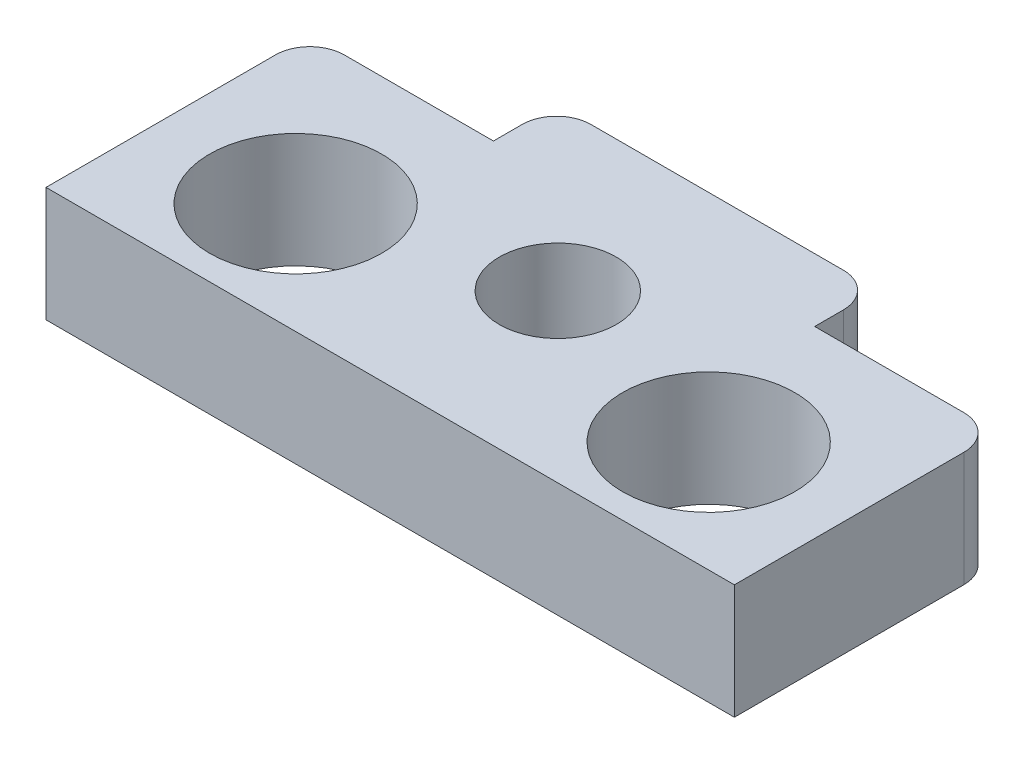
SolidWorks part; units mm, degrees
ref_plane "前视基准面" through (0, 0, 0) normal (0, 0, 1) x (1, 0, 0)
ref_plane "上视基准面" through (0, 0, 0) normal (0, 1, 0) x (1, 0, 0)
ref_plane "右视基准面" through (0, 0, 0) normal (1, 0, 0) x (0, 0, -1)
sketch "草图1" plane through (0, 0, 0) normal (0, 1, 0) x (1, 0, 0)
  line L0 (0, 0) -> (0, 28.5) construction
  line L1 (0, 0) -> (0, -15) construction
  line L2 (0, 0) -> (-30, 0)
  line L4 (-30, 0) -> (-30, 23)
  line L5 (-30, 23) -> (-14, 23)
  line L6 (-14, 23) -> (-14, 28.5)
  line L13 (-14, 28.5) -> (14, 28.5)
  line L14 (14, 28.5) -> (14, 23)
  line L15 (14, 23) -> (30, 23)
  line L16 (30, 23) -> (30, 0)
  line L17 (30, 0) -> (0, 0)
  point P0 (0, 0)
  dimension "D1" = 30
  dimension "D2" = 5.5
  dimension "D3" = 23
  dimension "D4" = 16
extrude "凸台-拉伸1" add sketch "草图1" along normal blind 10
sketch "草图2" plane through (0, 10, 0) normal (0, 1, 0) x (1, 0, 0)
  line L0 (0.1102, 18.5459) -> (0.1102, 1.5459) construction
  line L1 (-21.8898, 1.5459) -> (22.1102, 1.5459) construction
  line L2 (14, 28.5) -> (-14, 28.5) construction
  line L3 (-30, 0) -> (30, 0) construction
  circle A0 centre (18.1102, 9.65) radius 7.5
  circle A1 centre (-17.8898, 9.65) radius 7.5
  circle A2 centre (0.1102, 14.5) radius 5.1
  dimension "D1" = 15
  dimension "D2" = 36
  dimension "D3" = 9.65
  dimension "D4" = 10.2
  dimension "D5" = 14
fillet "圆角1" radius 3 4 edges at (30, 5, -23) (14, 5, -28.5) (-14, 5, -28.5) (-30, 5, -23)
extrude "切除-拉伸2" cut sketch "草图2" against normal blind 10
